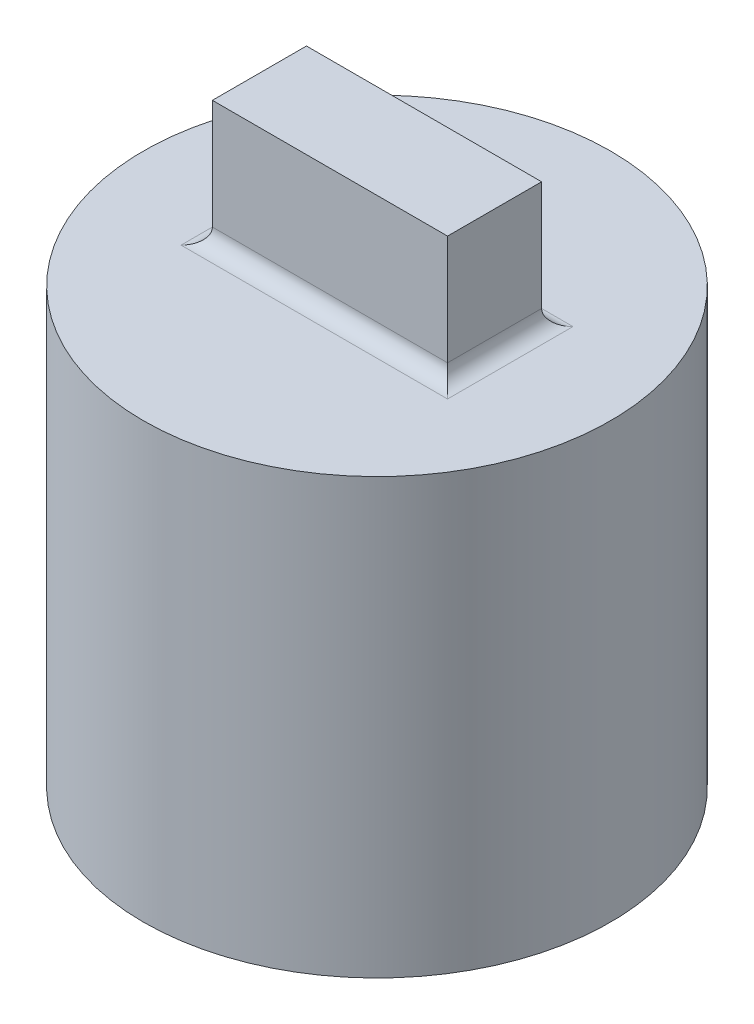
SolidWorks part; units mm, degrees
ref_plane "Front Plane" through (0, 0, 0) normal (0, 0, 1) x (1, 0, 0)
ref_plane "Top Plane" through (0, 0, 0) normal (0, 1, 0) x (1, 0, 0)
ref_plane "Right Plane" through (0, 0, 0) normal (1, 0, 0) x (0, 0, -1)
sketch "Sketch1" plane through (0, 0, 0) normal (0, 1, 0) x (1, 0, 0)
  circle A0 centre (0, 0) radius 14.9
  dimension "D1" = 29.8
extrude "Boss-Extrude1" add sketch "Sketch1" along normal blind 27.7
sketch "Sketch2" plane through (0, 0, 0) normal (0, -1, 0) x (1, 0, 0)
  circle A0 centre (0, 0) radius 13.4
  circle A1 centre (0, 0) radius 14.9 construction
  dimension "D1" = 1.5
extrude "Cut-Extrude1" cut sketch "Sketch2" against normal blind 10
sketch "Sketch3" plane through (0, 0, 0) normal (0, 0, 1) x (1, 0, 0)
  line L0 (14.9, 27.7) -> (-14.9, 27.7) construction
  line L1 (0, 27.7) -> (0, 15.0731) construction
  line L2 (7.5, 35.7) -> (-7.5, 35.7)
  line L3 (-7.5, 35.7) -> (-7.5, 27.7)
  line L4 (7.5, 35.7) -> (7.5, 27.7)
  line L5 (-7.5, 27.7) -> (7.5, 27.7)
  point P9 (0, 35.7)
  dimension "D1" = 7.5
  dimension "D2" = 8
extrude "Boss-Extrude2" add sketch "Sketch3" along normal blind 3 and the other way blind 3 contours L2 L3 L5 L4
fillet "Fillet1" radius 1 4 edges at (7.5, 27.7, 0) (0, 27.7, -3) (-7.5, 27.7, 0) (0, 27.7, 3)
